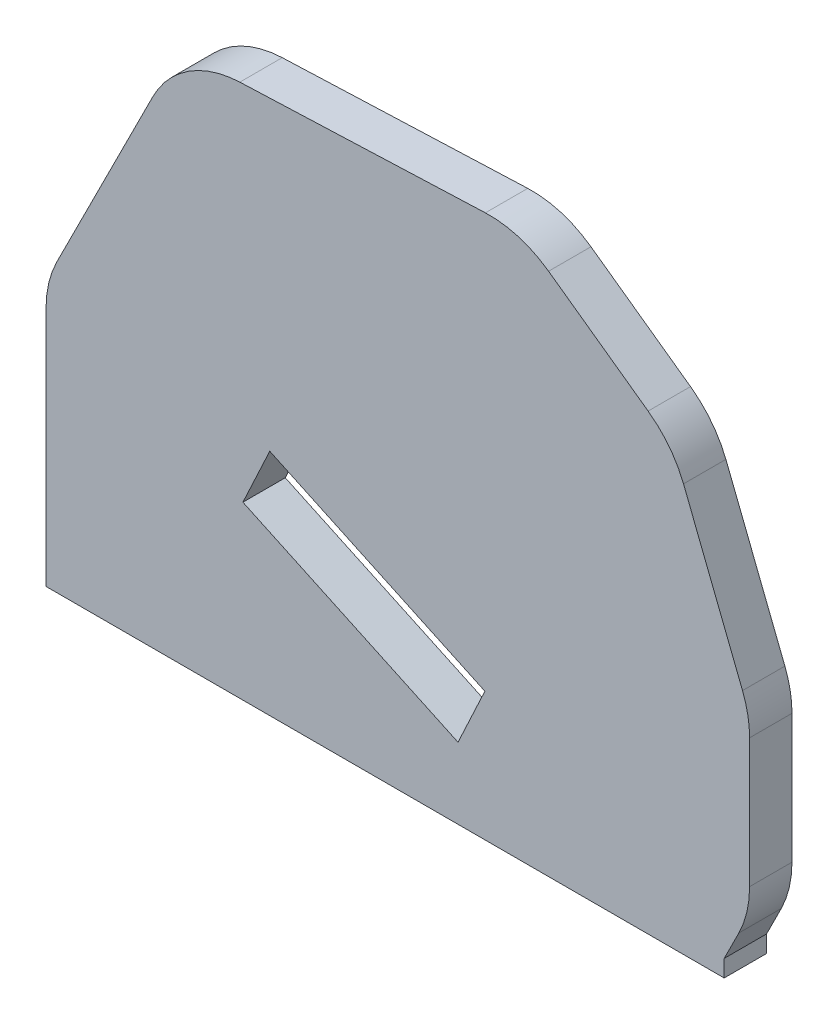
SolidWorks part; units mm, degrees
material "PBT General Purpose"
ref_plane "Front Plane" through (0, 0, 0) normal (0, 0, 1) x (1, 0, 0)
ref_plane "Top Plane" through (0, 0, 0) normal (0, 1, 0) x (1, 0, 0)
ref_plane "Right Plane" through (0, 0, 0) normal (1, 0, 0) x (0, 0, -1)
sketch "frame_outline" plane through (0, 0, 0) normal (0, 0, 1) x (1, 0, 0)
  line L0 (0, 0) -> (4, 0)
  line L1 (4, 0) -> (4, 0.1)
  line L2 (4, 0.1) -> (4.15, 0.4)
  line L3 (4.15, 0.4) -> (4.15, 1.4161)
  line L19 (4.15, 1.4161) -> (3.6952, 2.5687)
  line L20 (3.6952, 2.5687) -> (2.7971, 3.2123)
  line L21 (2.7971, 3.2123) -> (0.7894, 3.134)
  line L62 (0.7894, 3.134) -> (0, 1.5628)
  line L63 (0, 1.5628) -> (0, 0)
  line L64 (1.1613, 1.011) -> (2.4301, 0.4193)
  line L65 (1.1613, 1.011) -> (1.3198, 1.3509)
  line L66 (2.4301, 0.4193) -> (2.5886, 0.7592)
  line L67 (1.3198, 1.3509) -> (2.5886, 0.7592)
  line L68 (1.2405, 1.1809) -> (2.5094, 0.5893) construction
  dimension "D1" = 4
  dimension "D6" = 0.1
  dimension "D7" = 0.15
  dimension "D8" = 0.3
  dimension "D12" = 0.375
  dimension "D13" = 1.4
  dimension "D14" = 25
  dimension "D3" = 1.6
extrude "Boss-Extrude1" add sketch "frame_outline" along normal mid plane 0.25
fillet "Fillet1" radius 0.6 6 edges at (4.15, 0.4, 0) (4.15, 1.4161, 0) (3.6952, 2.5687, 0) (2.7971, 3.2123, 0) (0.7894, 3.134, 0) (0, 1.5628, 0)
equation "\"t\"= 0.25'thickness of the sheets"
equation "\"t_cf\"= 0.115'thickness of single carbon fiber layer"
equation "\"t_kapton\"= 0.025'thickness of single Kapton flex layer"
equation "\"t_fr4\"= 0.1'thickness of FR4 with copper layer"
equation "\"joint_flex\"= 0.1'Width of flextures gap"
equation "\"joint_flex_eff\"= 0.02'Width of flecture after castelation"
equation "\"joint_fold\"= 0.2'Width of folding joints for 90deg fold"
equation "\"gap_tolerance\"= 0.002'Width to have interfecence fit between carbon fiber inserts"
equation "\"assemble_angle\"= 90'Angle of assembly parts"
equation "\"D1@Boss-Extrude1\"=\"t\""
equation "\"D12@frame_outline\"=\"t\"*1.5"
equation "\"link_lift\"= 0.5'Actuation linkage amplification for the lift motion"
equation "\"link_swing\"= 0.45'Actuation linkage amplification for the swing motion"
